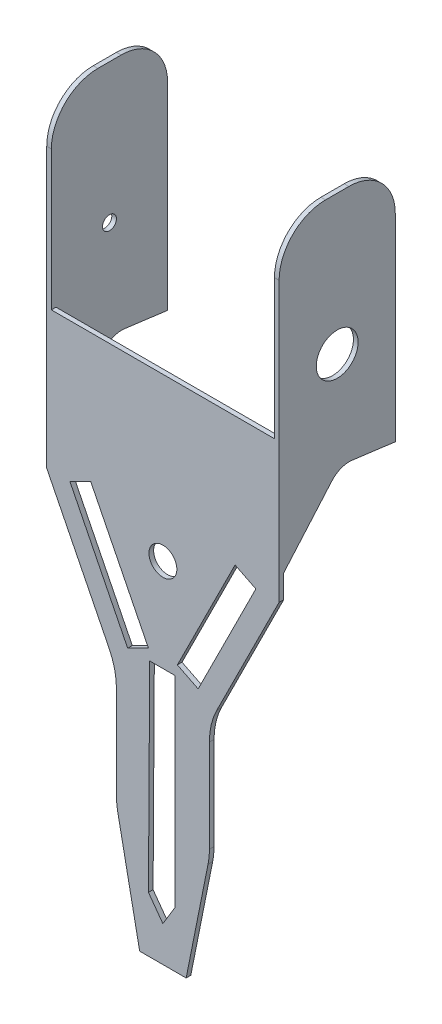
SolidWorks part; units mm, degrees
ref_plane "Alzado" through (0, 0, 0) normal (0, 0, 1) x (1, 0, 0)
ref_plane "Planta" through (0, 0, 0) normal (0, 1, 0) x (1, 0, 0)
ref_plane "Vista lateral" through (0, 0, 0) normal (1, 0, 0) x (0, 0, -1)
sketch "Croquis2" plane through (0, 0, 0) normal (0, 0, 1) x (1, 0, 0)
  line L1 (-32.8649, 52.5838) -> (17.1351, 52.5838)
  line L2 (-32.8649, 52.5838) -> (-32.8649, -97.4162)
  line L3 (-32.8649, -97.4162) -> (17.1351, -97.4162)
  line L4 (17.1351, 52.5838) -> (17.1351, -97.4162)
  dimension "D1" = 50
  dimension "D2" = 150
extrude "Saliente-Extruir1" add sketch "Croquis2" along normal blind 25
sketch "Croquis6" plane through (0, 0, 0) normal (0, 0, -1) x (-1, 0, 0)
  line L1 (-17.1351, 52.5838) -> (32.8649, 52.5838) construction
  line L2 (-16.1351, 52.5838) -> (-16.1351, 12.5838)
  line L4 (31.8649, 52.5838) -> (31.8649, 12.5838)
  line L5 (31.8649, 12.5838) -> (-16.1351, 12.5838)
  line L6 (-16.1351, 12.5838) -> (-16.1309, 12.4115)
  line L7 (-16.1351, 52.5838) -> (31.8649, 52.5838)
extrude "Cortar-Extruir1" cut sketch "Croquis6" against normal blind 25 contours L5 L4 L7 L2
shell "Vaciado2" thickness 1 removed face at (-7.8649, -97.4162, 12.5) removed face at (-7.8649, 12.5838, 12.5)
sketch "Croquis8" plane through (-32.8649, 0, 0) normal (-1, 0, 0) x (0, 0, 1)
  circle A0 centre (12.5, 22.5838) radius 1.5
  dimension "D1" = 3
extrude "Cortar-Extruir3" cut sketch "Croquis8" against normal blind 1
sketch "Croquis9" plane through (0, 0, 0) normal (0, 0, -1) x (-1, 0, 0)
  line L0 (-16.1351, 12.5838) -> (-16.1351, -97.4162)
  line L1 (32.8649, -97.4162) -> (-17.1351, -97.4162) construction
  line L2 (31.8649, 12.5838) -> (31.8649, -97.4162)
  line L3 (-16.1351, 12.5838) -> (31.8649, 12.5838)
  line L4 (-16.1351, -97.4162) -> (31.8649, -97.4162)
extrude "Cortar-Extruir4" cut sketch "Croquis9" against normal blind 10
sketch "Croquis10" plane through (-32.8649, 0, 0) normal (-1, 0, 0) x (0, 0, 1)
  line L0 (0, 0) -> (24, -12.4162)
  line L3 (24, -12.4162) -> (24, -97.4162)
  line L4 (25, -97.4162) -> (0, -97.4162) construction
  line L5 (24, -97.4162) -> (0, -97.4162)
  line L6 (0, -97.4162) -> (0, 0)
  dimension "D1" = 65
  dimension "D2" = 52.5838
extrude "Cortar-Extruir5" cut sketch "Croquis10" against normal blind 1
sketch "Croquis11" plane through (17.1351, 0, 0) normal (1, 0, 0) x (0, 0, -1)
  line L3 (-24, -12.4162) -> (-24, -97.4162)
  line L4 (-25, -97.4162) -> (0, -97.4162) construction
  line L5 (-24, -97.4162) -> (0, -97.4162)
  line L6 (0, -97.4162) -> (0, 0)
  line L7 (0, 0) -> (-24, -12.4162)
  circle A0 centre (-12.5, 22.5838) radius 1.5
  line M1 (0, -97.4162) -> (0, 52.5838)
  line M4 (-25, -97.4162) -> (0, -97.4162)
extrude "Cortar-Extruir6" cut sketch "Croquis11" against normal blind 1 contours L7 L3 M1 M4 region at (17.1351, -51.7417, 11.7277)
sketch "Croquis12" plane through (17.1351, 0, 0) normal (1, 0, 0) x (0, 0, -1)
  circle A0 centre (-12.5, 22.5838) radius 4.5
  dimension "D1" = 9
extrude "Cortar-Extruir7" cut sketch "Croquis12" against normal blind 1
sketch "Croquis13" plane through (0, 0, 25) normal (0, 0, 1) x (1, 0, 0)
  line L0 (-17.8649, -50.9572) -> (-17.8649, -70.9309)
  line L1 (-27.8649, -17.4162) -> (-23.3928, -15.1801)
  line L2 (-32.8649, -97.4162) -> (-12.8649, -97.4162)
  line L3 (-27.8649, -17.4162) -> (-15.4485, -42.249)
  line L4 (-32.8649, -17.4162) -> (-32.8649, -97.4162)
  line L5 (-32.8649, 52.5838) -> (-32.8649, -97.4162) construction
  line L6 (-32.8649, -17.4162) -> (-19.4485, -44.249)
  line L7 (-17.5736, -73.8726) -> (-12.8649, -97.4162)
  line L8 (-15.4485, -42.249) -> (-10.9764, -40.0129)
  line L9 (-2.8649, -97.4162) -> (1.8438, -73.8726)
  line L10 (2.1351, -70.9309) -> (2.1351, -50.9572)
  line L11 (3.7187, -44.249) -> (17.1351, -17.4162)
  line L12 (17.1351, -97.4162) -> (17.1351, 52.5838) construction
  line L13 (17.1351, -17.4162) -> (17.1351, -97.4162)
  line L14 (17.1351, -97.4162) -> (-2.8649, -97.4162)
  line L15 (-10.9764, -40.0129) -> (-23.3928, -15.1801)
  line L17 (12.1351, -17.4162) -> (-0.2813, -42.249)
  line L18 (-0.2813, -42.249) -> (-4.7534, -40.0129)
  line L19 (-4.7534, -40.0129) -> (7.663, -15.1801)
  line L20 (7.663, -15.1801) -> (12.1351, -17.4162)
  line L24 (-7.8649, -42.249) -> (-5.2855, -42.249)
  line L25 (-5.2855, -42.249) -> (-5.2855, -85.5126)
  line L26 (-5.2855, -85.5126) -> (-7.8649, -89.7959)
  line L27 (-7.8649, -89.7959) -> (-10.9764, -85.5126)
  line L28 (-10.9764, -85.5126) -> (-10.7092, -42.249)
  line L29 (-10.7092, -42.249) -> (-7.8649, -42.249)
  arc A0 (1.8438, -73.8726) -> (2.1351, -70.9309) centre (-12.8649, -70.9309) ccw
  arc A1 (2.1351, -50.9572) -> (3.7187, -44.249) centre (17.1351, -50.9572) cw
  arc A2 (-17.8649, -50.9572) -> (-19.4485, -44.249) centre (-32.8649, -50.9572) ccw
  arc A3 (-17.5736, -73.8726) -> (-17.8649, -70.9309) centre (-2.8649, -70.9309) cw
  circle A4 centre (-7.8649, -22.249) radius 3
  dimension "D1" = 80
  dimension "D2" = 15
extrude "Cortar-Extruir8" cut sketch "Croquis13" against normal blind 10
fillet "Redondeo1" radius 10 4 edges at (16.6351, 52.5838, 0) (16.6351, 52.5838, 25) (-32.3649, 52.5838, 0) (-32.3649, 52.5838, 25)
sketch "Croquis14" plane through (-32.8649, 0, 0) normal (-1, 0, 0) x (0, 0, 1)
  line L0 (0, 0) -> (9.2359, 1.2007)
  line L1 (13.6591, -0.4831) -> (24, -12.4162)
  line L2 (24, -12.4162) -> (0, 0)
  arc A0 (9.2359, 1.2007) -> (13.6591, -0.4831) centre (9.8805, -3.7575) cw
  dimension "D1" = 5
extrude "Cortar-Extruir9" cut sketch "Croquis14" against normal blind 50
